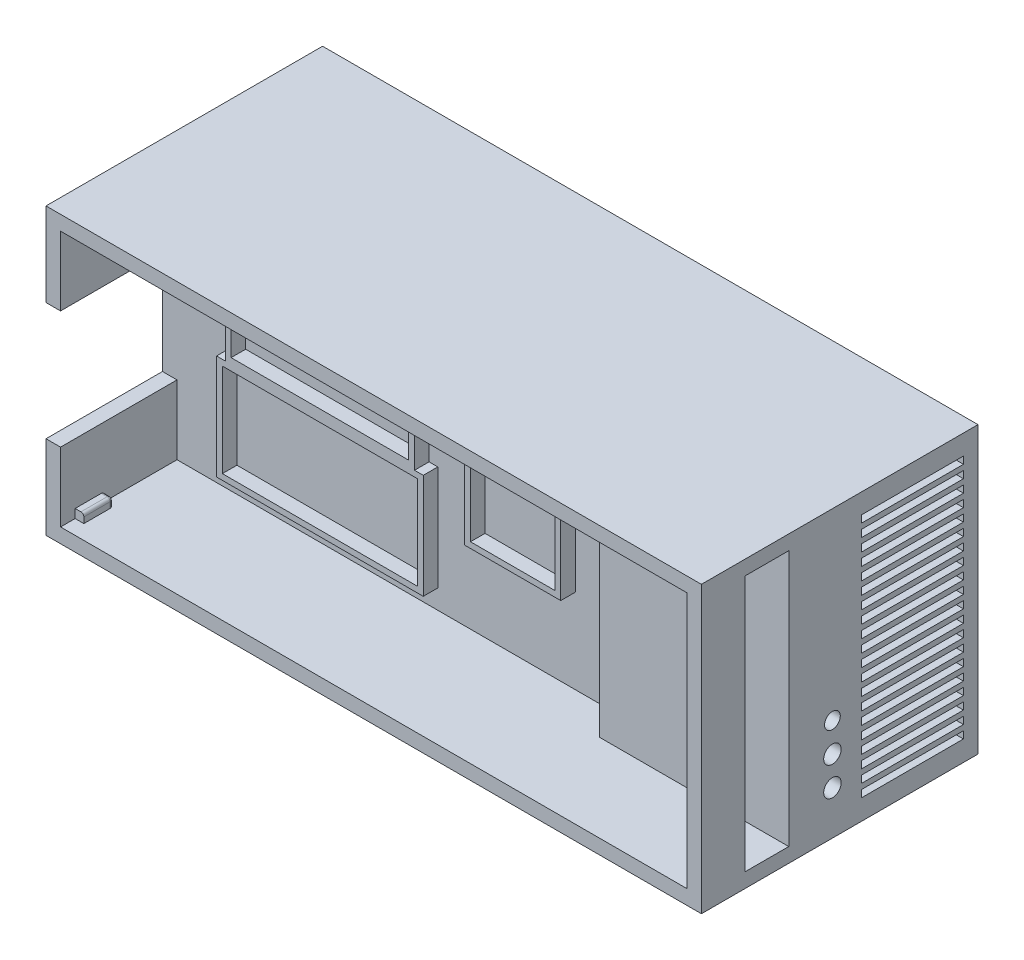
SolidWorks part; units mm, degrees
ref_plane "Front Plane" through (0, 0, 0) normal (0, 0, 1) x (1, 0, 0)
ref_plane "Top Plane" through (0, 0, 0) normal (0, 1, 0) x (1, 0, 0)
ref_plane "Right Plane" through (0, 0, 0) normal (1, 0, 0) x (0, 0, -1)
sketch "Sketch1" plane through (0, 0, 0) normal (0, 0, 1) x (1, 0, 0)
  line L0 (-73.9075, -12.793) -> (-73.9075, -55.793)
  line L1 (-73.9075, 32.207) -> (146.0925, 32.207)
  line L2 (-73.9075, 32.207) -> (-73.9075, 29.207)
  line L3 (-73.9075, -55.793) -> (146.0925, -55.793)
  line L4 (146.0925, 32.207) -> (146.0925, -55.793)
  line L5 (-73.9075, 32.207) -> (-66.4075, 29.207) construction
  line L6 (-73.9075, -55.793) -> (146.0925, 32.207) construction
  line L7 (-73.9075, 29.207) -> (-43.9075, 29.207)
  line L9 (-73.9075, -12.793) -> (-43.9075, -12.793)
  line L10 (-43.9075, 29.207) -> (-43.9075, -12.793)
  line L14 (-43.9075, 20.207) -> (146.0925, -55.793) construction
  point P4 (36.0925, -11.793)
  point P9 (-58.9075, 8.207)
  dimension "D1" = 220
  dimension "D2" = 88
  dimension "D3" = 3
  dimension "D4" = 30
  dimension "D5" = 42
extrude "Boss-Extrude1" add sketch "Sketch1" along normal blind 5
sketch "Sketch2" plane through (0, 0, 0) normal (0, 0, -1) x (-1, 0, 0)
  line L1 (-146.0925, 32.207) -> (73.9075, 32.207)
  line L2 (-146.0925, 32.207) -> (-146.0925, -55.793)
  line L3 (-146.0925, -55.793) -> (73.9075, -55.793)
  line L4 (73.9075, 32.207) -> (73.9075, -55.793)
  line L5 (-146.0925, 32.207) -> (73.9075, -55.793) construction
  line L6 (-146.0925, -55.793) -> (73.9075, 32.207) construction
  point P4 (-36.0925, -11.793)
sketch "Sketch3" plane through (0, 0, 5) normal (0, 0, 1) x (1, 0, 0)
  line L1 (-73.9075, 32.207) -> (146.0925, 32.207)
  line L2 (-73.9075, 32.207) -> (-73.9075, -55.793)
  line L3 (-73.9075, -55.793) -> (146.0925, -55.793)
  line L4 (146.0925, 32.207) -> (146.0925, -55.793)
  line L5 (-73.9075, 32.207) -> (146.0925, -55.793) construction
  line L6 (-73.9075, -55.793) -> (146.0925, 32.207) construction
  point P4 (36.0925, -11.793)
extrude "Boss-Extrude3" add sketch "Sketch3" along normal blind 5
sketch "Sketch4" plane through (0, -55.793, 0) normal (0, -1, 0) x (1, 0, 0)
  line L0 (146.0925, 0) -> (-73.9075, 0) construction
  line L1 (-73.9075, 10) -> (146.202, 10)
  line L2 (-73.9075, 10) -> (-73.9075, -40)
  line L3 (-73.9075, -40) -> (146.202, -40)
  line L4 (146.202, 10) -> (146.202, -40)
  line L5 (-73.9075, 10) -> (146.202, -40) construction
  line L6 (-73.9075, -40) -> (146.202, 10) construction
  point P4 (36.1473, -15)
  dimension "D1" = 40
extrude "Boss-Extrude4" add sketch "Sketch4" along normal blind 5
sketch "Sketch5" plane through (0, 0, -40) normal (0, 0, -1) x (-1, 0, 0)
  line L1 (-146.202, -60.793) -> (73.9075, -60.793)
  line L2 (-146.202, -60.793) -> (-146.202, 32.207)
  line L3 (-146.202, 32.207) -> (73.9075, 32.207)
  line L4 (73.9075, -60.793) -> (73.9075, 32.207)
  line L5 (-146.202, -60.793) -> (73.9075, 32.207) construction
  line L6 (-146.202, 32.207) -> (73.9075, -60.793) construction
  point P4 (-36.1473, -14.293)
extrude "Boss-Extrude5" add sketch "Sketch5" along normal blind 5
sketch "Sketch6" plane through (0, 32.207, 0) normal (0, 1, 0) x (1, 0, 0)
  line L1 (-73.9075, -10) -> (146.202, -10)
  line L2 (-73.9075, -10) -> (-73.9075, 45)
  line L3 (-73.9075, 45) -> (146.202, 45)
  line L4 (146.202, -10) -> (146.202, 45)
  line L5 (-73.9075, -10) -> (146.202, 45) construction
  line L6 (-73.9075, 45) -> (146.202, -10) construction
  point P4 (36.0925, 17.5)
  point P5 (36.1473, 17.5)
extrude "Boss-Extrude6" add sketch "Sketch6" along normal blind 5 and the other way blind 3.5181
sketch "Sketch7" plane through (0, 0, 10) normal (0, 0, 1) x (1, 0, 0)
  line L0 (146.0925, -55.793) -> (-73.9075, -55.793) construction
  line L1 (146.0925, 32.207) -> (116.0925, 32.207)
  line L2 (146.0925, 32.207) -> (146.0925, -55.793)
  line L3 (146.0925, -55.793) -> (116.0925, -55.793)
  line L4 (116.0925, 32.207) -> (116.0925, -55.793)
  line L5 (146.0925, 32.207) -> (116.0925, -55.793) construction
  line L6 (146.0925, -55.793) -> (116.0925, 32.207) construction
  point P4 (131.0925, -11.793)
  dimension "D1" = 30
extrude "Cut-Extrude2" cut sketch "Sketch7" against normal blind 13 contours L4 L3 L2 L1
sketch "Sketch9" plane through (0, -60.793, 0) normal (0, -1, 0) x (1, 0, 0)
  line L0 (-68.9075, 10) -> (-68.9075, -64.5271) construction
  line L1 (146.202, 10) -> (-73.9075, 10) construction
  line L2 (-73.9075, 10) -> (-73.9075, -45) construction
  line L3 (-73.9075, -17.5) -> (50.5126, -17.5) construction
  line L4 (-68.9075, -10) -> (-57.9075, -10)
  line L5 (-68.9075, -10) -> (-68.9075, -15)
  line L6 (-68.9075, -15) -> (-57.9075, -15)
  line L7 (-57.9075, -10) -> (-57.9075, -15)
  line L8 (-68.9075, -10) -> (-57.9075, -15) construction
  line L9 (-68.9075, -15) -> (-57.9075, -10) construction
  line L10 (146.0925, 0) -> (-73.9075, 0) construction
  line L11 (-68.9075, -20) -> (-57.9075, -20)
  line L12 (-57.9075, -25) -> (-57.9075, -20)
  line L13 (-68.9075, -25) -> (-57.9075, -25)
  line L14 (-68.9075, -25) -> (-68.9075, -20)
  point P10 (-63.4075, -12.5)
  dimension "D1" = 5
  dimension "D2" = 11
  dimension "D3" = 5
  dimension "D4" = 10
extrude "Cut-Extrude3" cut sketch "Sketch9" against normal blind 5
fillet "Fillet1" radius 5 2 edges at (-58.9075, -12.793, 0) (-43.9075, 7.9479, 0)
fillet "Fillet2" radius 2 8 edges at (-57.9075, -55.793, -22.5) (-63.4075, -55.793, -25) (-68.9075, -55.793, -22.5) (-63.4075, -55.793, -20) (-57.9075, -55.793, -12.5) (-63.4075, -55.793, -10) (-68.9075, -55.793, -12.5) (-63.4075, -55.793, -15)
sketch "Sketch11" plane through (146.202, 0, 0) normal (1, 0, 0) x (0, 0, -1)
  line L1 (-10, 37.207) -> (45, 37.207)
  line L2 (-10, 37.207) -> (-10, -60.793)
  line L3 (-10, -60.793) -> (45, -60.793)
  line L4 (45, 37.207) -> (45, -60.793)
  line L5 (-10, 37.207) -> (45, -60.793) construction
  line L6 (-10, -60.793) -> (45, 37.207) construction
  point P4 (17.5, -11.793)
extrude "Boss-Extrude7" add sketch "Sketch11" along normal blind 5
sketch "Sketch12" plane through (0, 0, 10) normal (0, 0, 1) x (1, 0, 0)
  line L0 (-68.9075, -55.793) -> (146.202, -55.793)
  line L1 (-73.9075, 37.207) -> (151.202, 37.207)
  line L2 (-73.9075, 37.207) -> (-73.9075, -60.793)
  line L3 (-73.9075, -60.793) -> (151.202, -60.793)
  line L4 (151.202, 37.207) -> (151.202, -60.793)
  line L5 (-73.9075, 37.207) -> (151.202, -60.793) construction
  line L6 (-73.9075, -60.793) -> (151.202, 37.207) construction
  line L7 (146.202, 32.207) -> (146.202, -55.793)
  line L8 (-68.9075, 32.207) -> (146.202, 32.207)
  line L9 (-68.9075, 32.207) -> (-68.9075, -55.793)
  point P4 (38.6473, -11.793)
  dimension "D1" = 5
extrude "Boss-Extrude8" add sketch "Sketch12" along normal blind 40
sketch "Sketch13" plane through (146.202, 0, 0) normal (-1, 0, 0) x (0, 0, 1)
  line L0 (20, 37.207) -> (20, -61.5232) construction
  line L1 (-45, 37.207) -> (50, 37.207) construction
  line L2 (0, 32.207) -> (0, -55.793) construction
  line L3 (50, 32.207) -> (10, 32.207) construction
  line L4 (20, 32.207) -> (35, 32.207)
  line L5 (20, 32.207) -> (20, -55.793)
  line L6 (20, -55.793) -> (35, -55.793)
  line L7 (35, 32.207) -> (35, -55.793)
  line L8 (20, 32.207) -> (35, -55.793) construction
  line L9 (20, -55.793) -> (35, 32.207) construction
  line L10 (-40, -55.793) -> (50, -55.793) construction
  point P10 (27.5, -11.793)
  dimension "D1" = 20
  dimension "D2" = 15
extrude "Cut-Extrude5" cut sketch "Sketch13" against normal blind 35 contours L7 L6 L5 L4
sketch "Sketch14" plane through (0, 0, 20) normal (0, 0, 1) x (1, 0, 0)
  line L0 (151.202, 32.207) -> (146.202, 32.207) construction
  line L1 (151.202, -55.793) -> (86.202, -55.793)
  line L2 (151.202, -55.793) -> (151.202, 32.207)
  line L3 (151.202, 32.207) -> (86.202, 32.207)
  line L4 (86.202, -55.793) -> (86.202, 32.207)
  line L5 (151.202, -55.793) -> (86.202, 32.207) construction
  line L6 (151.202, 32.207) -> (86.202, -55.793) construction
  point P4 (118.702, -11.793)
  dimension "D1" = 65
extrude "Boss-Extrude9" add sketch "Sketch14" against normal blind 5
sketch "Sketch15" plane through (0, 0, 10) normal (0, 0, 1) x (1, 0, 0)
  line L0 (146.0925, 32.207) -> (-73.9075, 32.207) construction
  line L1 (117.3832, 32.207) -> (86.202, 32.207)
  line L2 (117.3832, 32.207) -> (117.3832, -55.793)
  line L3 (117.3832, -55.793) -> (86.202, -55.793)
  line L4 (86.202, 32.207) -> (86.202, -55.793)
  line L5 (117.3832, 32.207) -> (86.202, -55.793) construction
  line L6 (117.3832, -55.793) -> (86.202, 32.207) construction
  point P4 (101.7926, -11.793)
extrude "Cut-Extrude6" cut sketch "Sketch15" against normal blind 15
fillet "Fillet3" radius 10 1 edges at (146.202, -11.793, 15)
fillet "Fillet4" radius 10 1 edges at (86.202, -11.793, 10)
fillet "Fillet5" radius 10 1 edges at (86.202, -11.793, 15)
sketch "Sketch17" plane through (151.202, 0, 0) normal (1, 0, 0) x (0, 0, -1)
  line L0 (-10, 37.207) -> (-10, -60.793) construction
  line L1 (45, 37.207) -> (-50, 37.207) construction
  line L2 (-50, -60.793) -> (45, -60.793) construction
  line L3 (-20, -55.793) -> (-20, 32.207) construction
  line L4 (-5, 37.207) -> (-5, -60.793) construction
  circle A0 centre (-5, -45.793) radius 3
  circle A1 centre (-5, -35.793) radius 3
  circle A2 centre (-5, -25.793) radius 2.7016
  dimension "D3" = 5.4032
  dimension "D4" = 6
  dimension "D5" = 6
  dimension "D1" = 10
  dimension "D2" = 5
  dimension "D6" = 15
  dimension "D7" = 10
  dimension "D8" = 10
extrude "Cut-Extrude7" cut sketch "Sketch17" against normal blind 15
sketch "Sketch18" plane through (0, 0, 20) normal (0, 0, 1) x (1, 0, 0)
  line L0 (146.0925, 32.207) -> (-73.9075, 32.207) construction
  line L1 (131.0925, 32.207) -> (146.0925, 32.207)
  line L2 (131.0925, 32.207) -> (131.0925, -55.793)
  line L3 (131.0925, -55.793) -> (146.0925, -55.793)
  line L4 (146.0925, 32.207) -> (146.0925, -55.793)
  line L5 (131.0925, 32.207) -> (146.0925, -55.793) construction
  line L6 (131.0925, -55.793) -> (146.0925, 32.207) construction
  point P4 (138.5925, -11.793)
  dimension "D1" = 15
sketch "Sketch20" plane through (0, 0, -45) normal (0, 0, -1) x (-1, 0, 0)
  line L0 (73.9075, -5.793) -> (-121.8039, -5.793) construction
  line L1 (73.9075, 32.207) -> (73.9075, -55.793) construction
  line L2 (-146.0925, -55.793) -> (73.9075, -55.793) construction
  circle A0 centre (38.9075, -5.793) radius 3
  dimension "D2" = 6
  dimension "D1" = 50
  dimension "D3" = 35
extrude "Cut-Extrude9" cut sketch "Sketch20" against normal blind 15
sketch "Sketch21" plane through (146.202, 0, 0) normal (-1, 0, 0) x (0, 0, 1)
  line L0 (-40, -55.793) -> (-40, 28.6889) construction
  line L1 (-40, -51.3372) -> (0, -51.3372)
  line L2 (-40, -51.3372) -> (-40, -53.793)
  line L3 (-40, -53.793) -> (0, -53.793)
  line L4 (0, -51.3372) -> (0, -53.793)
  line L5 (-40, -51.3372) -> (0, -53.793) construction
  line L6 (-40, -53.793) -> (0, -51.3372) construction
  line L7 (0, 32.207) -> (0, -55.793) construction
  line L8 (0, -55.793) -> (-40, -55.793) construction
  line L9 (-40, -47.0372) -> (-40, -49.493)
  line L10 (-40, -47.0372) -> (0, -47.0372)
  line L11 (0, -47.0372) -> (0, -49.493)
  line L12 (-40, -49.493) -> (0, -49.493)
  line L13 (-40, -42.7372) -> (-40, -45.193)
  line L14 (-40, -42.7372) -> (0, -42.7372)
  line L15 (0, -42.7372) -> (0, -45.193)
  line L16 (-40, -45.193) -> (0, -45.193)
  line L17 (-40, -38.4372) -> (-40, -40.893)
  line L18 (-40, -38.4372) -> (0, -38.4372)
  line L19 (0, -38.4372) -> (0, -40.893)
  line L20 (-40, -40.893) -> (0, -40.893)
  line L21 (-40, -34.1372) -> (-40, -36.593)
  line L22 (-40, -34.1372) -> (0, -34.1372)
  line L23 (0, -34.1372) -> (0, -36.593)
  line L24 (-40, -36.593) -> (0, -36.593)
  line L25 (-40, -29.8372) -> (-40, -32.293)
  line L26 (-40, -29.8372) -> (0, -29.8372)
  line L27 (0, -29.8372) -> (0, -32.293)
  line L28 (-40, -32.293) -> (0, -32.293)
  line L29 (-40, -25.5372) -> (-40, -27.993)
  line L30 (-40, -25.5372) -> (0, -25.5372)
  line L31 (0, -25.5372) -> (0, -27.993)
  line L32 (-40, -27.993) -> (0, -27.993)
  line L33 (-40, -21.2372) -> (-40, -23.693)
  line L34 (-40, -21.2372) -> (0, -21.2372)
  line L35 (0, -21.2372) -> (0, -23.693)
  line L36 (-40, -23.693) -> (0, -23.693)
  line L37 (-40, -16.9372) -> (-40, -19.393)
  line L38 (-40, -16.9372) -> (0, -16.9372)
  line L39 (0, -16.9372) -> (0, -19.393)
  line L40 (-40, -19.393) -> (0, -19.393)
  line L41 (-40, -12.6372) -> (-40, -15.093)
  line L42 (-40, -12.6372) -> (0, -12.6372)
  line L43 (0, -12.6372) -> (0, -15.093)
  line L44 (-40, -15.093) -> (0, -15.093)
  line L45 (-40, -8.3372) -> (-40, -10.793)
  line L46 (-40, -8.3372) -> (0, -8.3372)
  line L47 (0, -8.3372) -> (0, -10.793)
  line L48 (-40, -10.793) -> (0, -10.793)
  line L49 (-40, -4.0372) -> (-40, -6.493)
  line L50 (-40, -4.0372) -> (0, -4.0372)
  line L51 (0, -4.0372) -> (0, -6.493)
  line L52 (-40, -6.493) -> (0, -6.493)
  line L53 (-40, 0.2628) -> (-40, -2.193)
  line L54 (-40, 0.2628) -> (0, 0.2628)
  line L55 (0, 0.2628) -> (0, -2.193)
  line L56 (-40, -2.193) -> (0, -2.193)
  line L57 (-40, 4.5628) -> (-40, 2.107)
  line L58 (-40, 4.5628) -> (0, 4.5628)
  line L59 (0, 4.5628) -> (0, 2.107)
  line L60 (-40, 2.107) -> (0, 2.107)
  line L61 (-40, 8.8628) -> (-40, 6.407)
  line L62 (-40, 8.8628) -> (0, 8.8628)
  line L63 (0, 8.8628) -> (0, 6.407)
  line L64 (-40, 6.407) -> (0, 6.407)
  line L65 (-40, 13.1628) -> (-40, 10.707)
  line L66 (-40, 13.1628) -> (0, 13.1628)
  line L67 (0, 13.1628) -> (0, 10.707)
  line L68 (-40, 10.707) -> (0, 10.707)
  line L69 (-40, 17.4628) -> (-40, 15.007)
  line L70 (-40, 17.4628) -> (0, 17.4628)
  line L71 (0, 17.4628) -> (0, 15.007)
  line L72 (-40, 15.007) -> (0, 15.007)
  line L73 (-40, 21.7628) -> (-40, 19.307)
  line L74 (-40, 21.7628) -> (0, 21.7628)
  line L75 (0, 21.7628) -> (0, 19.307)
  line L76 (-40, 19.307) -> (0, 19.307)
  line L77 (-40, 26.0628) -> (-40, 23.607)
  line L78 (-40, 26.0628) -> (0, 26.0628)
  line L79 (0, 26.0628) -> (0, 23.607)
  line L80 (-40, 23.607) -> (0, 23.607)
  line L81 (-40, 30.3628) -> (-40, 27.907)
  line L82 (-40, 30.3628) -> (0, 30.3628)
  line L83 (0, 30.3628) -> (0, 27.907)
  line L84 (-40, 27.907) -> (0, 27.907)
  point P4 (-20, -52.5651)
  dimension "D1" = 2.4558
  dimension "D2" = 2
  dimension "D3" = 20
extrude "Cut-Extrude10" cut sketch "Sketch21" against normal blind 15
sketch "Sketch22" plane through (151.202, 0, 0) normal (1, 0, 0) x (0, 0, -1)
  line L0 (0, -53.793) -> (40, -53.793) construction
  line L1 (0, 30.3628) -> (5, 30.3628)
  line L2 (0, 30.3628) -> (0, -53.793)
  line L3 (0, -53.793) -> (5, -53.793)
  line L4 (5, 30.3628) -> (5, -53.793)
  line L5 (0, 30.3628) -> (5, -53.793) construction
  line L6 (0, -53.793) -> (5, 30.3628) construction
  point P4 (2.5, -11.7151)
  dimension "D1" = 5
extrude "Boss-Extrude11" add sketch "Sketch22" against normal blind 5
sketch "Sketch24" plane through (-68.9075, 0, 0) normal (1, 0, 0) x (0, 0, -1)
  line L0 (-10, 32.207) -> (-10, -55.793) construction
  line L2 (-10, -11.793) -> (-50, -11.793) construction
  line L3 (-50, 32.207) -> (-50, -55.793) construction
  line L5 (-50, 8.457) -> (-10, 8.457)
  line L6 (-50, 8.457) -> (-50, -32.043)
  line L7 (-50, -32.043) -> (-10, -32.043)
  line L8 (-10, 8.457) -> (-10, -32.043)
  line L9 (-50, 8.457) -> (-10, -32.043) construction
  line L10 (-50, -32.043) -> (-10, 8.457) construction
  point P10 (-30, -11.793)
  dimension "D1" = 40.5
extrude "Cut-Extrude11" cut sketch "Sketch24" against normal blind 5
sketch "Sketch25" plane through (0, 0, 10) normal (0, 0, 1) x (1, 0, 0)
  line L0 (-73.9075, -11.793) -> (76.202, -11.793) construction
  line L1 (-73.9075, -32.043) -> (-73.9075, 8.457) construction
  line L2 (76.202, -55.793) -> (76.202, 32.207) construction
  line L3 (-47.3343, 29.8621) -> (-47.3343, -13.1379)
  line L4 (36.889, 1.207) -> (65.889, 1.207)
  line L5 (36.889, 1.207) -> (36.889, -24.793)
  line L6 (36.889, -24.793) -> (65.889, -24.793)
  line L7 (65.889, 1.207) -> (65.889, -24.793)
  line L8 (36.889, 1.207) -> (65.889, -24.793) construction
  line L9 (36.889, -24.793) -> (65.889, 1.207) construction
  line L10 (-48.3343, -15.1379) -> (18.6657, -15.1379)
  line L11 (-48.3343, -15.1379) -> (-48.3343, -47.1379)
  line L12 (-48.3343, -47.1379) -> (18.6657, -47.1379)
  line L13 (18.6657, -15.1379) -> (18.6657, -47.1379)
  line L14 (-48.3343, -15.1379) -> (18.6657, -47.1379) construction
  line L15 (-48.3343, -47.1379) -> (18.6657, -15.1379) construction
  line L16 (-45.3343, 27.8621) -> (15.6657, 27.8621)
  line L17 (-45.3343, 27.8621) -> (-45.3343, -11.1379)
  line L18 (-45.3343, -11.1379) -> (15.6657, -11.1379)
  line L19 (15.6657, 27.8621) -> (15.6657, -11.1379)
  line L20 (-45.3343, 27.8621) -> (15.6657, -11.1379) construction
  line L21 (-45.3343, -11.1379) -> (15.6657, 27.8621) construction
  line L22 (-47.3343, -13.1379) -> (17.6657, -13.1379)
  line L23 (17.6657, 29.8621) -> (17.6657, -13.1379)
  line L24 (-47.3343, 29.8621) -> (17.6657, 29.8621)
  line L25 (-50.3343, -13.1379) -> (-50.3343, -49.1379)
  line L26 (-50.3343, -49.1379) -> (20.6657, -49.1379)
  line L27 (20.6657, -13.1379) -> (20.6657, -49.1379)
  line L28 (-50.3343, -13.1379) -> (20.6657, -13.1379)
  line L29 (34.889, 3.207) -> (34.889, -26.793)
  line L30 (34.889, -26.793) -> (67.889, -26.793)
  line L31 (67.889, 3.207) -> (67.889, -26.793)
  line L32 (34.889, 3.207) -> (67.889, 3.207)
  point P10 (51.389, -11.793)
  point P16 (-14.8343, -31.1379)
  point P23 (-14.8343, 8.3621)
  dimension "D1" = 29
  dimension "D2" = 26
  dimension "D3" = 67
  dimension "D4" = 32
  dimension "D5" = 25.5731
  dimension "D6" = 39
  dimension "D7" = 61
  dimension "D8" = 2
extrude "Boss-Extrude14" add sketch "Sketch25" along normal blind 5 contours L10 L13 L12 L11 | L5 L6 L7 L4 | L27 L26 L25 L28 | L19 L18 L17 L16 | L23 L22 L3 L24 | L29 L30 L31 L32
ref_plane "Plane1" through (0, 0, 45) normal (0, 0, 1) x (1, 0, 0)
sketch "Sketch26" plane through (0, 0, 45) normal (0, 0, 1) x (1, 0, 0)
  line L0 (143.202, 32.207) -> (146.202, 32.207)
  line L1 (-68.9075, 32.207) -> (-65.9075, 32.207)
  line L2 (-68.9075, 32.207) -> (-68.9075, 29.207)
  line L3 (-68.9075, 29.207) -> (-65.9075, 29.207)
  line L4 (-65.9075, 32.207) -> (-65.9075, 29.207)
  line L5 (-68.9075, 32.207) -> (-65.9075, 29.207) construction
  line L6 (-68.9075, 29.207) -> (-65.9075, 32.207) construction
  line L7 (143.202, 32.207) -> (143.202, 29.207)
  line L8 (143.202, 29.207) -> (146.202, 29.207)
  line L9 (146.202, 32.207) -> (146.202, 29.207)
  line L10 (143.202, 32.207) -> (146.202, 29.207) construction
  line L11 (143.202, 29.207) -> (146.202, 32.207) construction
  line L12 (146.202, -11.793) -> (-68.9075, -11.793) construction
  line L13 (146.202, -55.793) -> (146.202, 32.207) construction
  line L14 (-68.9075, -52.793) -> (-65.9075, -55.793) construction
  line L15 (-68.9075, -55.793) -> (-65.9075, -52.793) construction
  line L16 (-65.9075, -55.793) -> (-65.9075, -52.793)
  line L17 (-68.9075, -52.793) -> (-65.9075, -52.793)
  line L18 (-68.9075, -55.793) -> (-68.9075, -52.793)
  line L19 (-68.9075, -55.793) -> (-65.9075, -55.793)
  line L20 (143.202, -52.793) -> (146.202, -55.793) construction
  line L21 (143.202, -55.793) -> (146.202, -52.793) construction
  line L22 (146.202, -55.793) -> (146.202, -52.793)
  line L23 (143.202, -52.793) -> (146.202, -52.793)
  line L24 (143.202, -55.793) -> (143.202, -52.793)
  line L25 (143.202, -55.793) -> (146.202, -55.793)
  point P4 (-67.4075, 30.707)
  point P10 (144.702, 30.707)
  point P20 (-67.4075, -54.293)
  point P25 (144.702, -54.293)
  dimension "D1" = 3
  dimension "D2" = 3
  dimension "D3" = 3
  dimension "D4" = 3
extrude "Boss-Extrude16" add sketch "Sketch26" against normal blind 10
fillet "Fillet8" radius 1 3 edges at (-65.9075, 29.207, 40) (-65.9075, 30.707, 35) (-67.4075, 29.207, 35)
fillet "Fillet9" radius 1 9 edges at (143.202, -54.293, 35) (144.702, -52.793, 35) (143.202, -52.793, 40) (144.702, 29.207, 35) (143.202, 29.207, 40) (143.202, 30.707, 35) (-65.9075, -54.293, 35) (-67.4075, -52.793, 35) (-65.9075, -52.793, 40)
